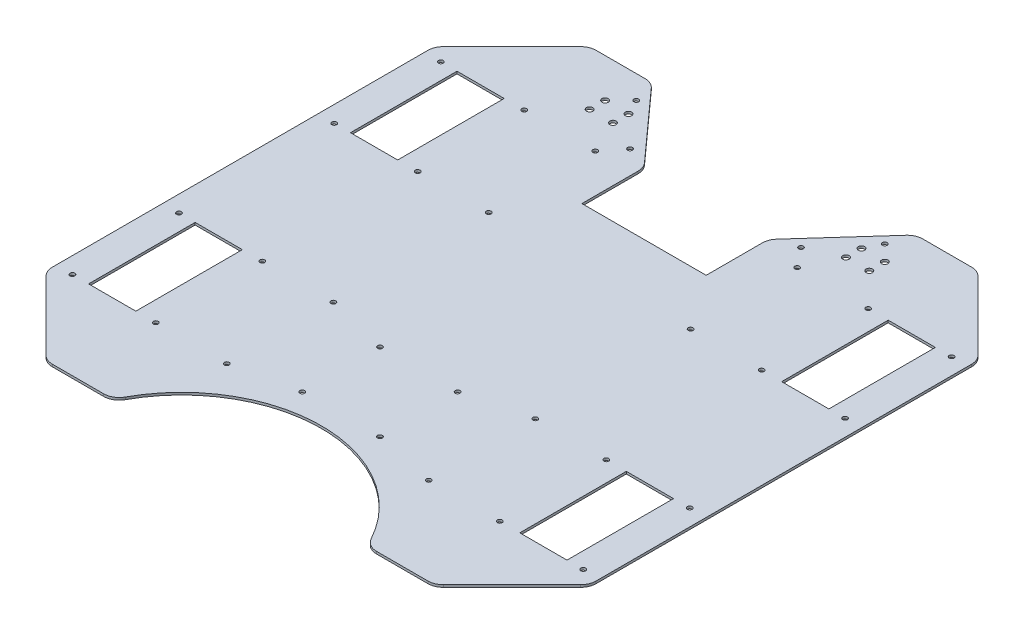
SolidWorks part; units mm, degrees
material "PMMA"
ref_plane "前视基准面" through (0, 0, 0) normal (0, 0, 1) x (1, 0, 0)
ref_plane "上视基准面" through (0, 0, 0) normal (0, 1, 0) x (1, 0, 0)
ref_plane "右视基准面" through (0, 0, 0) normal (1, 0, 0) x (0, 0, -1)
other "Configuration Table"
sketch "草图1" plane through (0, 0, 0) normal (0, 1, 0) x (1, 0, 0)
  line L0 (-125, 175) -> (-175, 125)
  line L1 (125, -175) -> (81.7103, -175)
  line L2 (175, -125) -> (175, 125)
  line L3 (125, 175) -> (85, 175)
  line L4 (-175, -125) -> (-175, 125)
  line L5 (-85, 175) -> (-40, 125)
  line L7 (125, 175) -> (175, 125)
  line L8 (175, -125) -> (125, -175)
  line L9 (-125, -175) -> (-175, -125)
  line L10 (40, 125) -> (85, 175)
  line L11 (-85, 175) -> (-125, 175)
  line L12 (40, 125) -> (40, 85)
  line L13 (40, 85) -> (-40, 85)
  line L14 (-40, 85) -> (-40, 125)
  line L15 (-153.994, 50) -> (-123.594, 50)
  line L16 (-123.594, 50) -> (-123.594, 118.58)
  line L17 (-123.594, 118.58) -> (-153.994, 118.58)
  line L18 (-153.994, 118.58) -> (-153.994, 50)
  line L19 (123.594, 50) -> (153.994, 50)
  line L20 (153.994, 50) -> (153.994, 118.58)
  line L21 (153.994, 118.58) -> (123.594, 118.58)
  line L22 (123.594, 118.58) -> (123.594, 50)
  line L23 (-175, 0) -> (175, 0) construction
  line L24 (-123.594, -118.58) -> (-153.994, -118.58)
  line L25 (-123.594, -50) -> (-123.594, -118.58)
  line L26 (-153.994, -50) -> (-123.594, -50)
  line L27 (-153.994, -118.58) -> (-153.994, -50)
  line L28 (153.994, -118.58) -> (123.594, -118.58)
  line L29 (153.994, -50) -> (153.994, -118.58)
  line L30 (123.594, -50) -> (153.994, -50)
  line L31 (123.594, -118.58) -> (123.594, -50)
  line L32 (-81.7103, -175) -> (-125, -175)
  line L33 (-80, 160) -> (-55, 131) construction
  line L34 (0, 85) -> (0, -124.4881) construction
  circle A0 centre (-55, 131) radius 1.55
  circle A1 centre (-80, 160) radius 1.55
  circle A2 centre (55, 131) radius 1.55
  circle A3 centre (80, 160) radius 1.55
  circle A4 centre (-65, 118.58) radius 1.55
  circle A5 centre (-65, 50) radius 1.55
  circle A6 centre (-110.72, 50) radius 1.55
  circle A7 centre (-110.72, 118.58) radius 1.55
  circle A12 centre (-164.434, 118.58) radius 1.55
  circle A13 centre (-164.434, 50) radius 1.55
  circle A14 centre (-65, -118.58) radius 1.55
  circle A15 centre (-65, -50) radius 1.55
  circle A16 centre (-110.72, -50) radius 1.55
  circle A17 centre (-110.72, -118.58) radius 1.55
  circle A18 centre (-164.434, -50) radius 1.55
  circle A19 centre (-164.434, -118.58) radius 1.55
  circle A20 centre (65, 50) radius 1.55
  circle A21 centre (110.72, 50) radius 1.55
  circle A22 centre (110.72, 118.58) radius 1.55
  circle A23 centre (65, 118.58) radius 1.55
  circle A24 centre (164.434, 118.58) radius 1.55
  circle A25 centre (164.434, 50) radius 1.55
  circle A26 centre (164.434, -118.58) radius 1.55
  circle A27 centre (164.434, -50) radius 1.55
  circle A28 centre (110.72, -50) radius 1.55
  circle A29 centre (110.72, -118.58) radius 1.55
  circle A30 centre (65, -118.58) radius 1.55
  circle A31 centre (65, -50) radius 1.55
  arc A32 (-81.7103, -175) -> (81.7103, -175) centre (0, -212.7283) cw
  circle A33 centre (25, -60) radius 1.55
  circle A34 centre (25, -110) radius 1.55
  circle A35 centre (-25, -60) radius 1.55
  circle A36 centre (-25, -110) radius 1.55
  circle A37 centre (-75, 150) radius 2.05
  circle A38 centre (-75, 140) radius 2.05
  circle A39 centre (-90, 140) radius 2.05
  circle A40 centre (-90, 150) radius 2.05
  circle A41 centre (75, 150) radius 2.05
  circle A42 centre (90, 150) radius 2.05
  circle A43 centre (90, 140) radius 2.05
  circle A44 centre (75, 140) radius 2.05
  point P0 (0, 0)
  point P1 (-85, 175)
  point P2 (85, 175)
  point P3 (40, 125)
  point P4 (-40, 125)
  point P6 (125, 175)
  point P8 (175, 125)
  point P10 (175, -125)
  point P11 (125, -175)
  point P12 (-125, -175)
  point P13 (-175, -125)
  point P24 (-80, 160)
  point P25 (-55, 131)
  point P26 (55, 131)
  point P27 (80, 160)
  point P36 (-164.434, 118.58)
  point P37 (-164.434, 50)
  point P38 (-153.994, 118.58)
  point P39 (-123.594, 50)
  point P40 (-110.72, 118.58)
  point P41 (-110.72, 50)
  point P42 (-65, 118.58)
  point P43 (-65, 50)
  point P47 (-123.594, 118.58)
  point P53 (-153.994, 50)
  point P66 (-40, 85)
  point P67 (40, 85)
  point P70 (110.72, 50)
  point P71 (65, 50)
  point P72 (123.594, 50)
  point P73 (153.994, 50)
  point P74 (164.434, 50)
  point P75 (65, 118.58)
  point P76 (110.72, 118.58)
  point P77 (123.594, 118.58)
  point P78 (153.994, 118.58)
  point P81 (164.434, 118.58)
  point P85 (-65, -118.58)
  point P88 (-65, -50)
  point P91 (-110.72, -50)
  point P94 (-110.72, -118.58)
  point P101 (-164.434, -50)
  point P104 (-164.434, -118.58)
  point P118 (164.434, -118.58)
  point P121 (164.434, -50)
  point P128 (110.72, -50)
  point P131 (110.72, -118.58)
  point P134 (65, -118.58)
  point P137 (65, -50)
  point P157 (90, 140)
  point P158 (75, 140)
  point P159 (75, 150)
  point P160 (90, 150)
  dimension "D29" = 3.1
  dimension "D30" = 3.1
  dimension "D31" = 3.1
  dimension "D32" = 3.1
  dimension "D40" = 3.1
  dimension "D41" = 3.1
  dimension "D42" = 3.1
  dimension "D43" = 3.1
  dimension "D44" = 3.1
  dimension "D45" = 3.1
  dimension "D46" = 3.1
  dimension "D47" = 3.1
  dimension "D48" = 3.1
  dimension "D49" = 3.1
  dimension "D60" = 3.1
  dimension "D61" = 3.1
  dimension "D62" = 43.2897
  dimension "D63" = 90
  dimension "D67" = 3.1
  dimension "D68" = 3.1
  dimension "D69" = 3.1
  dimension "D70" = 3.1
  dimension "D75" = 4.1
  dimension "D76" = 4.1
  dimension "D77" = 4.1
  dimension "D78" = 4.1
  dimension "D1" = 175
  dimension "D2" = 175
  dimension "D3" = 125
  dimension "D4" = 125
  dimension "D5" = 125
  dimension "D6" = 125
  dimension "D7" = 125
  dimension "D8" = 125
  dimension "D9" = 125
  dimension "D10" = 125
  dimension "D11" = 175
  dimension "D12" = 175
  dimension "D13" = 40
  dimension "D14" = 40
  dimension "D15" = 85
  dimension "D16" = 85
  dimension "D17" = 125
  dimension "D18" = 125
  dimension "D19" = 40
  dimension "D20" = 45
  dimension "D21" = 160
  dimension "D22" = 160
  dimension "D23" = 80
  dimension "D24" = 80
  dimension "D25" = 55
  dimension "D26" = 131
  dimension "D27" = 55
  dimension "D28" = 131
  dimension "D33" = 50
  dimension "D34" = 118.58
  dimension "D35" = 65
  dimension "D36" = 45.72
  dimension "D37" = 12.874
  dimension "D38" = 30.4
  dimension "D39" = 10.44
  dimension "D50" = 40
  dimension "D51" = 40
  dimension "D52" = 85
  dimension "D53" = 85
  dimension "D54" = 138.013
  dimension "D55" = 65
  dimension "D56" = 45.72
  dimension "D57" = 12.874
  dimension "D58" = 30.4
  dimension "D59" = 10.44
  dimension "D64" = 0
  dimension "D65" = 25
  dimension "D66" = 25
  dimension "D71" = 60
  dimension "D72" = 50
  dimension "D73" = 15
  dimension "D74" = 10
  dimension "D79" = 75
  dimension "D80" = 90
  dimension "D81" = 150
extrude "凸台-拉伸1" add sketch "草图1" along normal blind 1.5 contours A1 | A0 | L8 L1 A32 L32 L9 L4 L0 L11 L5 L14 L13 L12 L10 L3 L7 L2 | A5 | A3 | A2 | A4 | A7 | A12 | L16 L17 L18 L15 | A6 | L21 L22 L19 L20 | A13 | A16 | A17 | A14 | A15 | A18 | A19 | L25 L24 L27 L26 | A20 | A21 | A22 | A23 | A24 | A25 | A28 | A26 | A27 | L28 L31 L30 L29 | A30 | A31 | A29 | A35 | A36 | A33 | A34 | A39 | A40 | A37 | A38 | A43 | A42 | A41 | A44
fillet "圆角1" radius 10 1 edges at (-40, 0.75, -125)
fillet "圆角2" radius 10 1 edges at (40, 0.75, -125)
fillet "圆角3" radius 10 12 edges at (-85, 0.75, -175) (85, 0.75, -175) (125, 0.75, -175) (175, 0.75, -125) (175, 0.75, 125) (125, 0.75, 175) (81.7103, 0.75, 175) (-81.7103, 0.75, 175) (-125, 0.75, 175) (-175, 0.75, 125) (-175, 0.75, -125) (-125, 0.75, -175)
